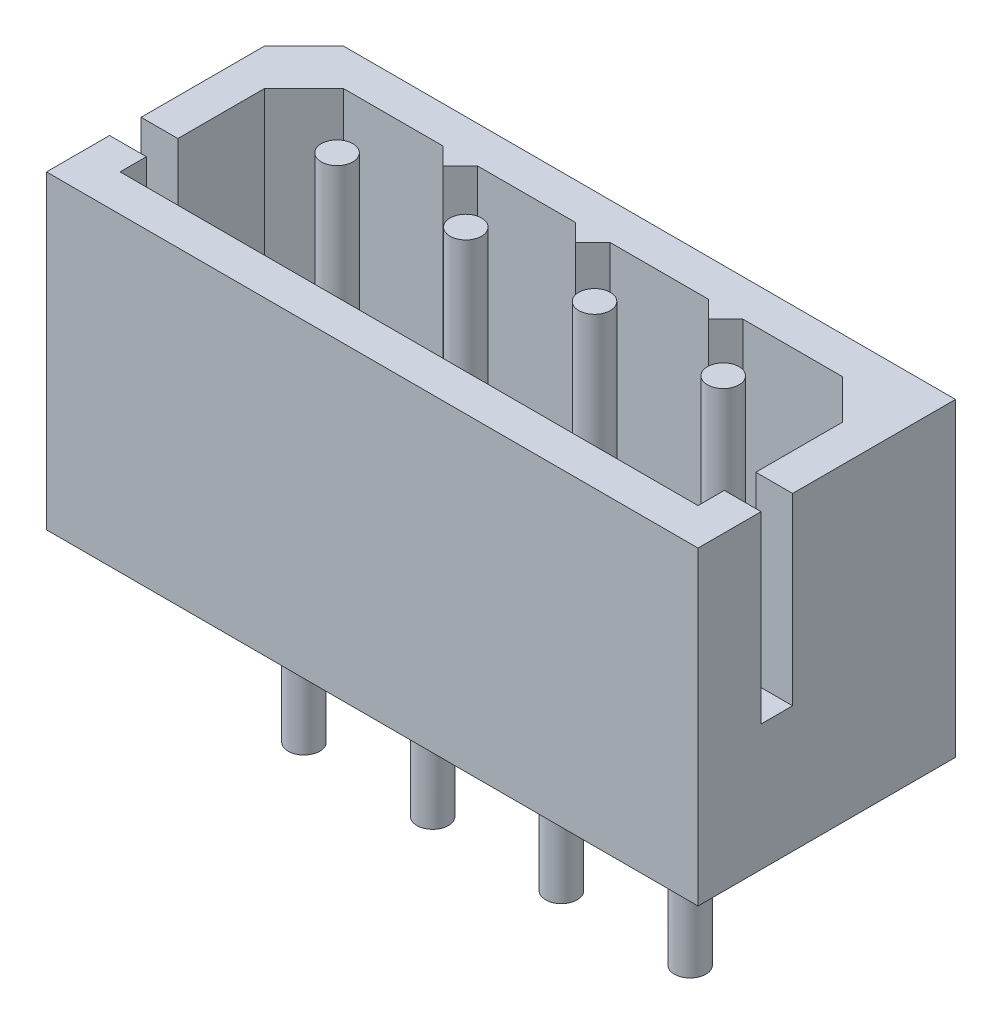
SolidWorks part; units mm, degrees
ref_plane "Front Plane" through (0, 0, 0) normal (0, 0, 1) x (1, 0, 0)
ref_plane "Top Plane" through (0, 0, 0) normal (0, 1, 0) x (1, 0, 0)
ref_plane "Right Plane" through (0, 0, 0) normal (1, 0, 0) x (0, 0, -1)
sketch "Sketch1" plane through (0, 0, 0) normal (0, 1, 0) x (1, 0, 0)
  line L0 (-5.45, 2.45) -> (-6.2, 1.7)
  line L1 (-5.45, 2.45) -> (6.2, 2.45)
  line L2 (-6.2, 1.7) -> (-6.2, -2.45)
  line L3 (-6.2, -2.45) -> (6.2, -2.45)
  line L4 (6.2, 2.45) -> (6.2, -2.45)
  line L5 (-6.2, 2.45) -> (6.2, -2.45) construction
  line L6 (-6.2, -2.45) -> (6.2, 2.45) construction
  point P0 (0, 0)
  dimension "D1" = 4.9
  dimension "D2" = 12.4
extrude "Boss-Extrude1" add sketch "Sketch1" against normal blind 5.9
sketch "Sketch2" plane through (0, -5.9, 0) normal (0, -1, 0) x (1, 0, 0)
  line L0 (-6.2, 0) -> (6.2, 0) construction
  line L1 (-6.2, -1.7) -> (-6.2, 2.45) construction
  line L2 (6.2, 2.45) -> (6.2, -2.45) construction
  line L3 (0, 2.45) -> (0, -2.45) construction
  line L4 (-6.2, 2.45) -> (6.2, 2.45) construction
  line L5 (6.2, -2.45) -> (-5.45, -2.45) construction
  line L6 (-3.75, 0) -> (-1.3, 0) construction
  line L7 (-6.2, -1.7) -> (-6.2, 2.45) construction
  line L8 (6.2, -2.45) -> (-5.45, -2.45) construction
  circle A0 centre (-3.75, 0) radius 0.3
  circle A1 centre (-1.3, 0) radius 0.3
  circle A2 centre (1.15, 0) radius 0.3
  circle A3 centre (3.6, 0) radius 0.3
  dimension "D1" = 0.6
  dimension "D2" = 2.45
  dimension "D5" = 2.45
  dimension "D4" = 2.45
  dimension "D3" = 4
extrude "Boss-Extrude2" add sketch "Sketch2" along normal blind 3.5
sketch "Sketch3" plane through (0, 0, 0) normal (0, 1, 0) x (1, 0, 0)
  line L0 (-6.2, -2.45) -> (6.2, -2.45) construction
  line L1 (-4.75, 1.75) -> (4.75, 1.75)
  line L2 (-5.5, 1) -> (-5.5, -0.65)
  line L3 (-5.5, -1.75) -> (5.5, -1.75)
  line L4 (5.5, 1) -> (5.5, -0.65)
  line L5 (-5.5, 1.75) -> (5.5, -1.75) construction
  line L6 (-5.5, -1.75) -> (5.5, 1.75) construction
  line L7 (-5.5, 0.63) -> (5.5, 0.63) construction
  line L8 (-3.75, 0.63) -> (-1.3, 0.63) construction
  line L9 (-2.525, 1.75) -> (-2.525, -1.75) construction
  line L10 (-2.525, 1.4218) -> (-2.8532, 1.75)
  line L11 (-2.525, 1.4218) -> (-2.1968, 1.75)
  line L13 (0, 1.4218) -> (-0.3282, 1.75)
  line L14 (0, 1.4218) -> (0.3282, 1.75)
  line L15 (2.525, 1.4218) -> (2.1968, 1.75)
  line L16 (2.525, 1.4218) -> (2.8532, 1.75)
  line L17 (6.2, -0.65) -> (5.5, -0.65)
  line L18 (-4.75, 1.75) -> (-5.5, 1)
  line L19 (4.75, 1.75) -> (5.5, 1)
  line L20 (-5.5, -1.25) -> (-6.2, -1.25)
  line L21 (-6.2, 1.7) -> (-6.2, -2.45) construction
  line L22 (-6.2, -1.25) -> (-6.2, -0.65)
  line L23 (-6.2, -0.65) -> (-5.5, -0.65)
  line L24 (-5.5, -1.25) -> (-5.5, -1.75)
  line L25 (0, -1.75) -> (0, 1.75) construction
  line L26 (6.2, -1.25) -> (6.2, -0.65)
  line L27 (5.5, -1.25) -> (6.2, -1.25)
  line L28 (5.5, -1.25) -> (5.5, -1.75)
  circle A0 centre (-3.75, 0.63) radius 0.3
  circle A1 centre (-1.3, 0.63) radius 0.3
  circle A2 centre (1.15, 0.63) radius 0.3
  circle A3 centre (3.6, 0.63) radius 0.3
  point P0 (0, 0)
  line M11 (6.2, -2.45) -> (6.2, 2.45)
  line M14 (-6.2, 1.7) -> (-6.2, -2.45)
  dimension "D4" = 1.75
  dimension "D5" = 0.6
  dimension "D8" = 2.975
  dimension "D1" = 11
  dimension "D2" = 0.7
  dimension "D3" = 2.38
  dimension "D7" = 2.45
  dimension "D9" = 45
  dimension "D10" = 45
  dimension "D11" = 0.6565
  dimension "D14" = 0.6
  dimension "D15" = 0.5
  dimension "D6" = 4
  dimension "D12" = 3
extrude "Cut-Extrude1" cut sketch "Sketch3" against normal blind 3.5 contours L28 L27 L17 L4 L19 L1 L16 L15 L14 L13 L11 L10 L18 L2 L23 L20 L24 L3 A3 A2 A1 A0 M11 M14 region at (0.0023, 0, 0.0773)
